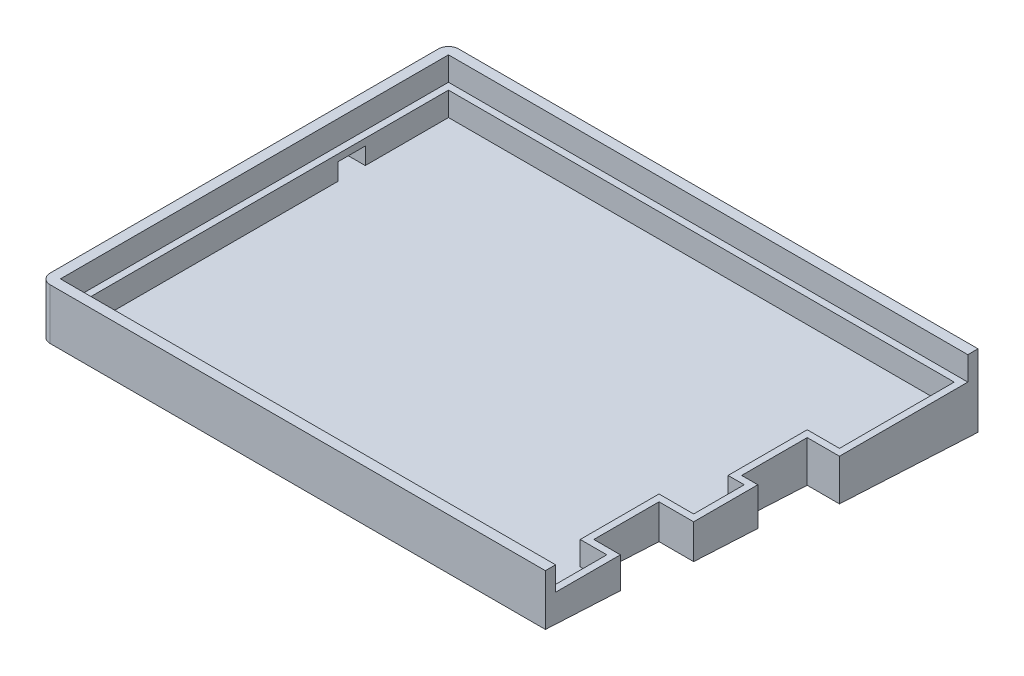
SolidWorks part; units mm, degrees
ref_plane "Front Plane" through (0, 0, 0) normal (0, 0, 1) x (1, 0, 0)
ref_plane "Top Plane" through (0, 0, 0) normal (0, 1, 0) x (1, 0, 0)
ref_plane "Right Plane" through (0, 0, 0) normal (1, 0, 0) x (0, 0, -1)
sketch "Sketch1" plane through (0, 0, 0) normal (0, 1, 0) x (1, 0, 0)
  line L0 (0, 0) -> (138, 0)
  line L1 (0, 0) -> (0, 114.29)
  line L2 (0, 114.29) -> (152.94, 114.29)
  line L3 (152.94, 114.29) -> (152.94, 76.49)
  line L4 (152.94, 76.49) -> (143.44, 76.49)
  line L5 (143.44, 76.49) -> (143.44, 57.19)
  line L6 (143.44, 57.19) -> (148.2, 57.19)
  line L7 (148.2, 57.19) -> (148.2, 38.29)
  line L8 (148.2, 38.29) -> (138, 38.29)
  line L9 (138, 38.29) -> (138, 0)
  line L10 (-3, -3) -> (138, -3)
  line L11 (-3, -3) -> (-3, 117.29)
  line L12 (-3, 117.29) -> (152.94, 117.29)
  line L13 (138, -3) -> (138, 0)
  line L14 (152.94, 117.29) -> (152.94, 114.29)
  line L15 (138, 0) -> (152.94, 0)
  line L16 (152.94, 0) -> (152.94, 76.49)
  line L17 (138, -3) -> (152.94, -3)
  line L18 (152.94, -3) -> (152.94, 0)
  dimension "D1" = 138
  dimension "D2" = 114.29
  dimension "D3" = 152.94
  dimension "D4" = 37.8
  dimension "D5" = 9.5
  dimension "D6" = 19.3
  dimension "D7" = 4.76
  dimension "D8" = 18.9
  dimension "D9" = 3
extrude "Boss-Extrude1" add sketch "Sketch1" along normal blind 14 contours L14 L12 L11 L10 L13 L0 L1 L2 region at (69, 0, 1.9694)
extrude "Boss-Extrude2" add sketch "Sketch1<3>" against normal blind 1 contours L9 L8 L7 L6 L5 L4 L3 L2 L1 L0 | L14 L12 L11 L10 L13 L0 L1 L2 region at (72.9075, 0, -58.3956) region at (69, 0, 1.9694)
sketch "Sketch1<3>" plane through (0, 0, 0) normal (0, 1, 0) x (1, 0, 0) same geometry as "Sketch1"
sketch "Sketch2" plane through (152.94, 0, 0) normal (1, 0, 0) x (0, 0, -1)
  line L0 (117.29, 0) -> (117.29, -7.3041)
  line L1 (117.29, 14) -> (117.29, -1) construction
  line L2 (117.29, -7.3041) -> (-3, -1)
  line L3 (-3, -1) -> (-3, 0)
  line L4 (-3, 14) -> (-3, -1) construction
  line L5 (-3, 0) -> (117.29, 0)
  line L6 (117.29, -1) -> (76.49, -1) construction
  dimension "D1" = 3
extrude "Boss-Extrude3" add sketch "Sketch2" against normal up to surface (155.94 mm away) up to face at (-3, 6.5, -57.145)
extrude "Cut-Extrude1" cut sketch "Sketch1<5>" against normal blind 10 contours L17 L18 L15 L13 | L15 L16 L4 L5 L6 L7 L8 L9 region at (145.47, 0, 1.5) region at (146.6009, 0, -32.5258)
sketch "Sketch1<5>" plane through (0, 0, 0) normal (0, 1, 0) x (1, 0, 0) same geometry as "Sketch1"
sketch "Sketch3" plane through (138, 0, 0) normal (1, 0, 0) x (0, 0, -1)
  line L0 (19.09, 0) -> (19.09, -2.1577)
  line L1 (0, 0) -> (38.29, 0) construction
  line L2 (38.29, -3.1639) -> (-3, -1) construction
  line L3 (0, 0) -> (114.29, 0) construction
  line L4 (-3, 14) -> (-3, -1) construction
  line L5 (0, 14) -> (0, 0) construction
  line L6 (-3, 14) -> (0, 14) construction
  line L7 (38.29, -3.1639) -> (-3, -1)
  line L8 (0, 0) -> (114.29, 0)
  line L9 (-3, 14) -> (-3, -1)
  line L10 (0, 14) -> (0, 0)
  line L11 (-3, 14) -> (0, 14)
  line L12 (38.29, -3.1639) -> (38.29, 0) construction
  line M1 (-3, 14) -> (-3, -1)
  line M2 (-3, -1) -> (38.29, -3.1639)
  line M4 (38.29, 0) -> (0, 0)
  line M5 (0, 0) -> (0, 14)
  line M6 (0, 14) -> (-3, 14)
  dimension "D1" = 19.2
extrude "Boss-Extrude4" add sketch "Sketch3" along normal blind 7.83 contours L0 M4 M5 M6 M1 M2 region at (138, -1.0788, -18.8163)
fillet "Fillet1" radius 3 2 edges at (-3, 6.5, 3) (-3, 3.3479, -117.29)
sketch "Sketch4" plane through (0, 0, 0) normal (0, 1, 0) x (1, 0, 0)
  line L0 (150.94, 112.29) -> (2, 112.29)
  line L1 (2, 112.29) -> (2, 2)
  line L2 (2, 2) -> (143.83, 2)
  line L3 (143.83, 2) -> (143.83, 17.09)
  line L4 (143.83, 17.09) -> (136, 17.09)
  line L5 (136, 17.09) -> (136, 40.29)
  line L6 (136, 40.29) -> (146.2, 40.29)
  line L7 (146.2, 40.29) -> (146.2, 55.19)
  line L8 (146.2, 55.19) -> (141.44, 55.19)
  line L9 (141.44, 55.19) -> (141.44, 78.49)
  line L10 (141.44, 78.49) -> (150.94, 78.49)
  line L11 (150.94, 78.49) -> (150.94, 112.29)
  line L12 (0, 0) -> (145.83, 0)
  line L13 (145.83, 0) -> (145.83, 19.09)
  line L14 (145.83, 19.09) -> (138, 19.09)
  line L15 (138, 19.09) -> (138, 38.29)
  line L16 (138, 38.29) -> (148.2, 38.29)
  line L17 (148.2, 38.29) -> (148.2, 57.19)
  line L18 (148.2, 57.19) -> (143.44, 57.19)
  line L19 (143.44, 57.19) -> (143.44, 76.49)
  line L20 (143.44, 76.49) -> (152.94, 76.49)
  line L21 (152.94, 76.49) -> (152.94, 114.29)
  line L22 (152.94, 114.29) -> (0, 114.29)
  line L23 (0, 114.29) -> (0, 0)
  line L24 (0, 0) -> (145.83, 0)
  line L25 (145.83, 0) -> (145.83, 19.09)
  line L26 (145.83, 19.09) -> (138, 19.09)
  line L27 (138, 19.09) -> (138, 38.29)
  line L28 (138, 38.29) -> (148.2, 38.29)
  line L29 (148.2, 38.29) -> (148.2, 57.19)
  line L30 (148.2, 57.19) -> (143.44, 57.19)
  line L31 (143.44, 57.19) -> (143.44, 76.49)
  line L32 (143.44, 76.49) -> (152.94, 76.49)
  line L33 (152.94, 76.49) -> (152.94, 114.29)
  line L34 (152.94, 114.29) -> (0, 114.29)
  line L35 (0, 114.29) -> (0, 0)
  dimension "D1" = 0
  dimension "D2" = 2
extrude "Boss-Extrude5" add sketch "Sketch4" along normal blind 7
sketch "Sketch5" plane through (2, 0, 0) normal (1, 0, 0) x (0, 0, -1)
  line L0 (87.79, 7) -> (87.79, 0)
  line L1 (112.29, 7) -> (2, 7) construction
  line L2 (112.29, 0) -> (2, 0) construction
  line L3 (112.29, 7) -> (112.29, 0) construction
  line L4 (79.69, 7) -> (79.69, 0)
  line L5 (79.69, 5) -> (87.79, 5)
  line L6 (79.69, 0) -> (87.79, 0)
  line M4 (2, 0) -> (112.29, 0)
  dimension "D1" = 24.5
  dimension "D2" = 8.1
  dimension "D3" = 5
extrude "Cut-Extrude2" cut sketch "Sketch5" against normal up to surface (5 mm away) contours L5 L4 L0 M4 region at (2, 2.5, -83.74) up to face at (-3, 4.924, -57.145)
